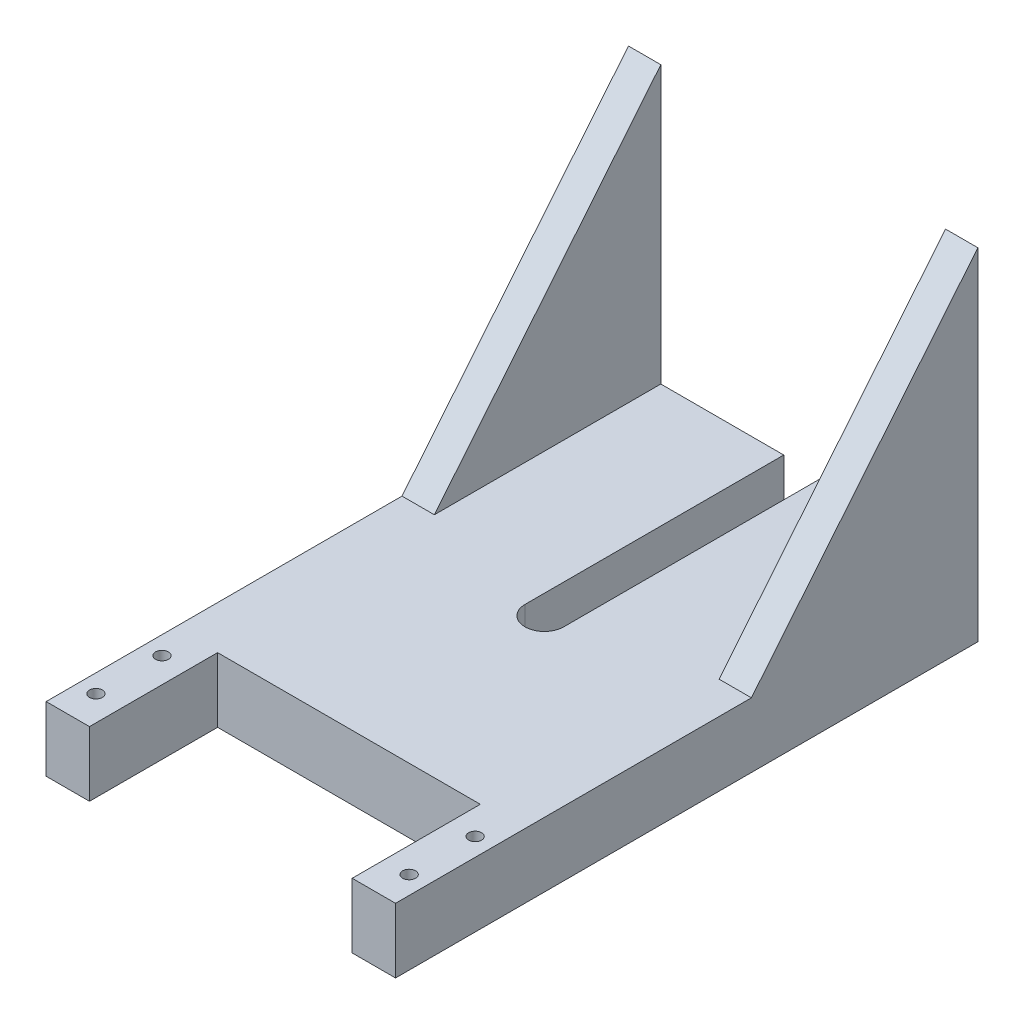
SolidWorks part; units mm, degrees
ref_plane "Front Plane" through (0, 0, 0) normal (0, 0, 1) x (1, 0, 0)
ref_plane "Top Plane" through (0, 0, 0) normal (0, 1, 0) x (1, 0, 0)
ref_plane "Right Plane" through (0, 0, 0) normal (1, 0, 0) x (0, 0, -1)
sketch "Sketch1" plane through (0, 0, 0) normal (0, 0, 1) x (1, 0, 0)
  line L0 (-16.0284, 532.1756) -> (37.9716, 532.1756)
  line L1 (-16.0284, 532.1756) -> (-16.0284, 522.1756)
  line L2 (-16.0284, 522.1756) -> (37.9716, 522.1756)
  line L3 (37.9716, 532.1756) -> (37.9716, 522.1756)
  dimension "D1" = 54
  dimension "D2" = 10
extrude "Boss-Extrude1" add sketch "Sketch1" along normal blind 90 contours L0 L3 L2 L1
sketch "Sketch2" plane through (0, 522.1756, 0) normal (0, -1, 0) x (1, 0, 0)
  line L0 (-16.0284, 90) -> (37.9716, 90) construction
  line L1 (-9.3284, 90) -> (31.2716, 90)
  line L2 (-9.3284, 90) -> (-9.3284, 70.2)
  line L3 (-9.3284, 70.2) -> (31.2716, 70.2)
  line L4 (31.2716, 90) -> (31.2716, 70.2)
  line L5 (10.9716, 70.2) -> (10.9716, 0) construction
  line L7 (-16.0284, 0) -> (37.9716, 0) construction
  dimension "D1" = 40.6
  dimension "D2" = 19.8
extrude "Cut-Extrude1" cut sketch "Sketch2" against normal through all
sketch "Sketch4" plane through (0, 532.1756, 0) normal (0, 1, 0) x (1, 0, 0)
  line L0 (10.9716, -70.2) -> (10.9716, 0) construction
  line L1 (-9.3284, -70.2) -> (31.2716, -70.2) construction
  line L2 (-16.0284, 0) -> (37.9716, 0) construction
  line L3 (10.9716, -40) -> (10.9716, 0) construction
  line L4 (7.9716, -40) -> (7.9716, 0)
  line L5 (13.9716, -40) -> (13.9716, 0)
  arc A0 (7.9716, -40) -> (13.9716, -40) centre (10.9716, -40) ccw
  arc A1 (13.9716, 0) -> (7.9716, 0) centre (10.9716, 0) ccw
  point P7 (10.9716, -20)
extrude "Cut-Extrude2" cut sketch "Sketch4" against normal through all
sketch "Sketch7" plane through (-16.0284, 0, 0) normal (-1, 0, 0) x (0, 0, 1)
  line L0 (35, 532.1756) -> (0, 574.9183)
  line L1 (90, 532.1756) -> (0, 532.1756) construction
  line L2 (0, 656.2827) -> (0, 356.2827) construction
  line L3 (0, 574.9183) -> (0, 532.1756)
  line L4 (0, 532.1756) -> (35, 532.1756)
extrude "Boss-Extrude4" add sketch "Sketch7" against normal blind 5
sketch "Sketch8" plane through (37.9716, 0, 0) normal (1, 0, 0) x (0, 0, -1)
  line L0 (-35, 532.1756) -> (0, 574.9183)
  line L1 (0, 574.9183) -> (0, 532.1756)
  line L2 (0, 532.1756) -> (-35, 532.1756)
extrude "Boss-Extrude5" add sketch "Sketch8" against normal blind 5
sketch "Sketch9" plane through (0, 522.1756, 0) normal (0, -1, 0) x (1, 0, 0)
  line L0 (-13.2284, 85.1) -> (35.1716, 85.1) construction
  line L3 (-13.2284, 74.9) -> (35.1716, 74.9) construction
  line L6 (-13.2284, 85.1) -> (-13.2284, 74.9) construction
  line L7 (35.1716, 74.9) -> (35.1716, 85.1) construction
  circle A0 centre (-13.2284, 85.1) radius 1
  circle A1 centre (-13.2284, 74.9) radius 1
  circle A2 centre (35.1716, 74.9) radius 1
  circle A3 centre (35.1716, 85.1) radius 1
extrude "Cut-Extrude3" cut sketch "Sketch9" against normal through all
